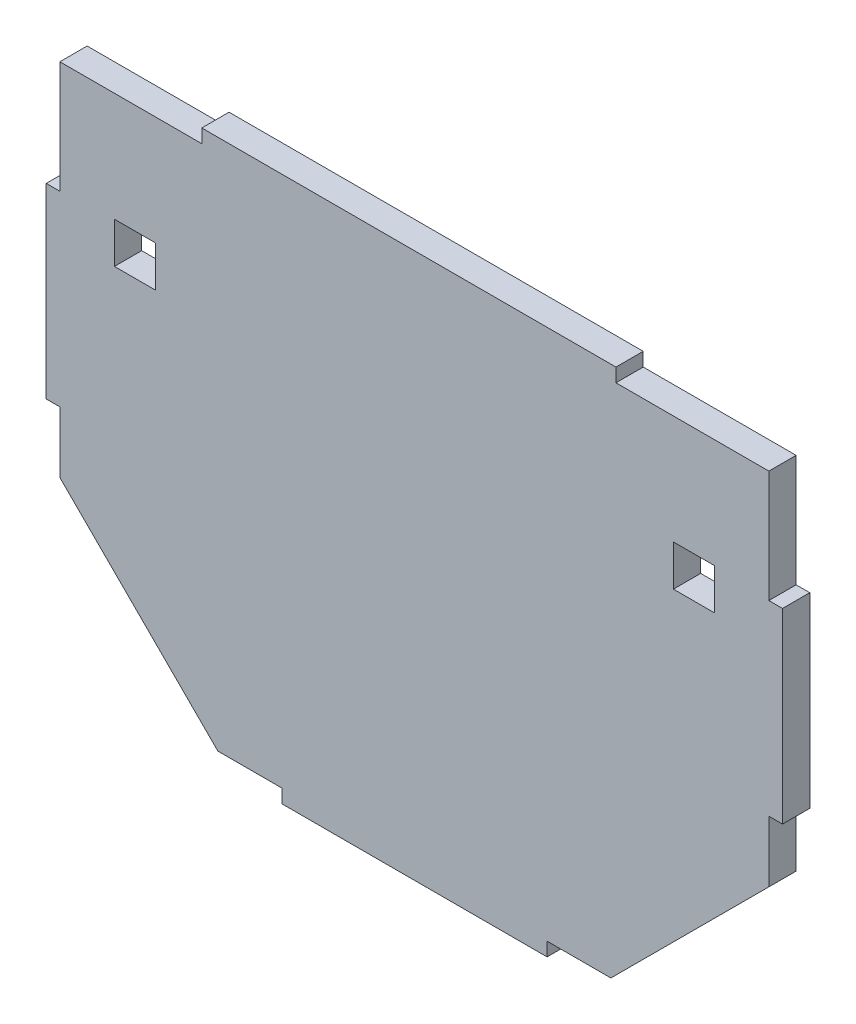
SolidWorks part; units mm, degrees
ref_plane "Front Plane" through (0, 0, 0) normal (0, 0, 1) x (1, 0, 0)
ref_plane "Top Plane" through (0, 0, 0) normal (0, 1, 0) x (1, 0, 0)
ref_plane "Right Plane" through (0, 0, 0) normal (1, 0, 0) x (0, 0, -1)
sketch "Sketch1" plane through (0, 0, 0) normal (0, 0, 1) x (1, 0, 0)
  line L0 (412.0154, 1072.6191) -> (767.6154, 1072.6191) construction
  line L1 (767.6154, 1072.6191) -> (767.6154, 886.9451) construction
  line L2 (767.6154, 886.9451) -> (686.5894, 805.9673) construction
  line L3 (686.5894, 805.9673) -> (493.0414, 805.9673) construction
  line L4 (493.0414, 805.9673) -> (412.0154, 886.9451) construction
  line L5 (412.0154, 886.9451) -> (412.0154, 1072.6191) construction
  line L6 (424.7154, 892.2078) -> (424.7154, 920.7157)
  line L7 (424.7154, 1059.9191) -> (490.8067, 1059.9191)
  line L8 (754.9154, 1059.9191) -> (754.9154, 1007.6919)
  line L9 (754.9154, 892.2078) -> (681.3311, 818.6673)
  line L10 (681.3311, 818.6673) -> (651.6344, 818.6673)
  line L11 (498.2997, 818.6673) -> (424.7154, 892.2078)
  line L21 (424.7154, 1007.6919) -> (424.7154, 1059.9191)
  line L22 (424.7154, 892.2078) -> (424.7154, 1059.9191) construction
  line L23 (754.9154, 920.7157) -> (754.9154, 892.2078)
  line L24 (754.9154, 1059.9191) -> (754.9154, 892.2078) construction
  line L25 (528.0648, 818.6673) -> (498.2997, 818.6673)
  line L26 (681.3311, 818.6673) -> (498.2997, 818.6673) construction
  line L30 (683.7, 1059.9191) -> (754.9154, 1059.9191)
  line L31 (424.7154, 1059.9191) -> (754.9154, 1059.9191) construction
  line L32 (424.7154, 920.7157) -> (418.3654, 920.7157)
  line L33 (418.3654, 920.7157) -> (418.3654, 1007.6919)
  line L34 (418.3654, 1007.6919) -> (424.7154, 1007.6919)
  line L35 (490.8067, 1059.9191) -> (490.8067, 1066.2691)
  line L38 (754.9154, 1007.6919) -> (761.2654, 1007.6919)
  line L39 (761.2654, 1007.6919) -> (761.2654, 920.7157)
  line L40 (761.2654, 920.7157) -> (754.9154, 920.7157)
  line L41 (651.6344, 818.6673) -> (651.6344, 812.3173)
  line L42 (651.6344, 812.3173) -> (528.0648, 812.3173)
  line L43 (528.0648, 812.3173) -> (528.0648, 818.6673)
  line L44 (683.7, 1059.9191) -> (683.7, 1066.2691)
  line L45 (683.7, 1066.2691) -> (490.8067, 1066.2691)
  dimension "D1" = 355.6
  dimension "D2" = 185.674
  dimension "D3" = 114.554
  dimension "D4" = 193.548
  dimension "D6" = 6.35
  dimension "D7" = 6.35
  dimension "D8" = 6.35
  dimension "D9" = 6.35
  dimension "D5" = 12.7
extrude "Boss-Extrude1" add sketch "Sketch1" along normal blind 12.7
sketch "Sketch2" plane through (0, 0, 12.7) normal (0, 0, 1) x (1, 0, 0)
  line L0 (424.7154, 1059.9191) -> (424.7154, 1007.6919) construction
  line L5 (450.1154, 1009.1191) -> (469.1654, 1009.1191)
  line L6 (450.1154, 1009.1191) -> (450.1154, 990.0691)
  line L7 (450.1154, 990.0691) -> (469.1654, 990.0691)
  line L8 (469.1654, 1009.1191) -> (469.1654, 990.0691)
  line L9 (710.4654, 1009.1191) -> (729.5154, 1009.1191)
  line L10 (710.4654, 1009.1191) -> (710.4654, 990.0691)
  line L11 (710.4654, 990.0691) -> (729.5154, 990.0691)
  line L12 (729.5154, 1009.1191) -> (729.5154, 990.0691)
  line L13 (490.8067, 1059.9191) -> (424.7154, 1059.9191) construction
  line L14 (754.9154, 1007.6919) -> (754.9154, 1059.9191) construction
  line L15 (754.9154, 1059.9191) -> (683.7, 1059.9191) construction
  dimension "D1" = 25.4
  dimension "D2" = 50.8
  dimension "D3" = 25.4
  dimension "D4" = 50.8
  dimension "D5" = 19.05
extrude "Cut-Extrude1" cut sketch "Sketch2" against normal through all
